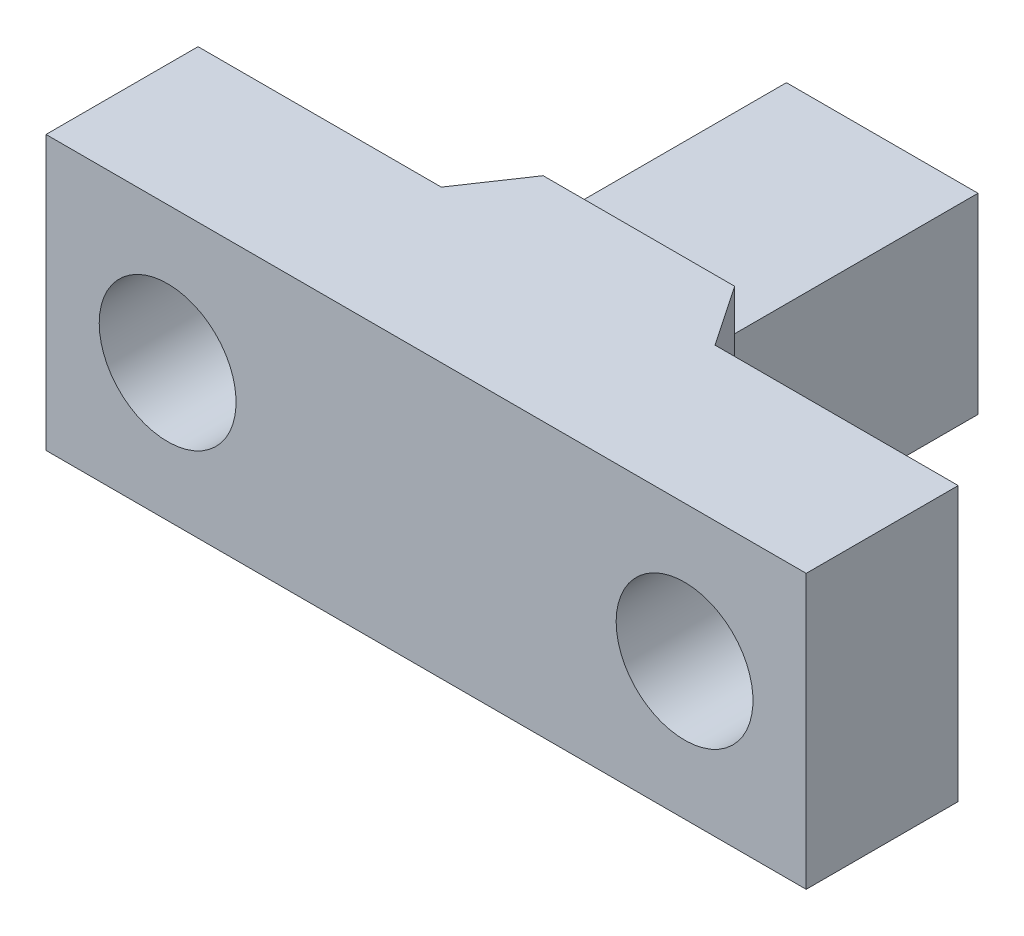
SolidWorks part; units mm, degrees
ref_plane "Plano frontal" through (0, 0, 0) normal (0, 0, 1) x (1, 0, 0)
ref_plane "Plano superior" through (0, 0, 0) normal (0, 1, 0) x (1, 0, 0)
ref_plane "Plano direito" through (0, 0, 0) normal (1, 0, 0) x (0, 0, -1)
sketch "Esboço1" plane through (0, 0, 0) normal (0, 1, 0) x (1, 0, 0)
  line L0 (0, 0) -> (25, 0)
  line L1 (25, 0) -> (25, 5)
  line L2 (25, 5) -> (17, 5)
  line L3 (17, 5) -> (17, 15)
  line L5 (8, 15) -> (8, 5)
  line L6 (8, 5) -> (0, 5)
  line L7 (0, 5) -> (0, 0)
  line L13 (12.5, 15) -> (12.5, 0) construction
  line L14 (8, 15) -> (17, 15)
  point P11 (12.5, 15)
  dimension "D2" = 9
  dimension "D3" = 5
  dimension "D4" = 25
  dimension "D6" = 10
extrude "Ressalto-extrusão1" add sketch "Esboço1" along normal blind 9
sketch "Esboço2" plane through (0, 0, -15) normal (0, 0, -1) x (-1, 0, 0)
  line L0 (-17, 4.5) -> (-8, 4.5) construction
  line L1 (-17, 9) -> (-8, 9)
  line L2 (-17, 9) -> (-17, 0)
  line L3 (-17, 0) -> (-8, 0)
  line L4 (-8, 9) -> (-8, 0)
  line L5 (-15.65, 7.65) -> (-9.35, 7.65)
  line L6 (-15.65, 7.65) -> (-15.65, 1.35)
  line L7 (-15.65, 1.35) -> (-9.35, 1.35)
  line L8 (-9.35, 7.65) -> (-9.35, 1.35)
  line L9 (-12.5, 9) -> (-12.5, 0) construction
  line L10 (-17, 9) -> (-8, 9) construction
  point P14 (-12.5, 7.65)
  point P15 (-9.35, 4.5)
  dimension "D1" = 6.3
  dimension "D2" = 6.3
  dimension "D3" = 1.35
extrude "Corte-extrusão1" cut sketch "Esboço2" against normal blind 8
sketch "Esboço3" plane through (0, 0, -5) normal (0, 0, -1) x (-1, 0, 0)
  line L0 (-25, 4.5) -> (0, 4.5) construction
  line L1 (-25, 9) -> (-25, 0) construction
  line L2 (0, 9) -> (0, 0) construction
  circle A0 centre (-4, 4.5) radius 2.25
  circle A1 centre (-21, 4.5) radius 2.25
  dimension "D1" = 4.5
  dimension "D2" = 4.5
  dimension "D3" = 4
  dimension "D4" = 4
extrude "Corte-extrusão2" cut sketch "Esboço3" against normal through all
chamfer "Chanfro2" distance 2 distance2 1.35 2 edges at (8, 4.5, -7) (17, 4.5, -7) first distance on face at (8, 4.5, -6) first distance on face at (17, 4.5, -6)
